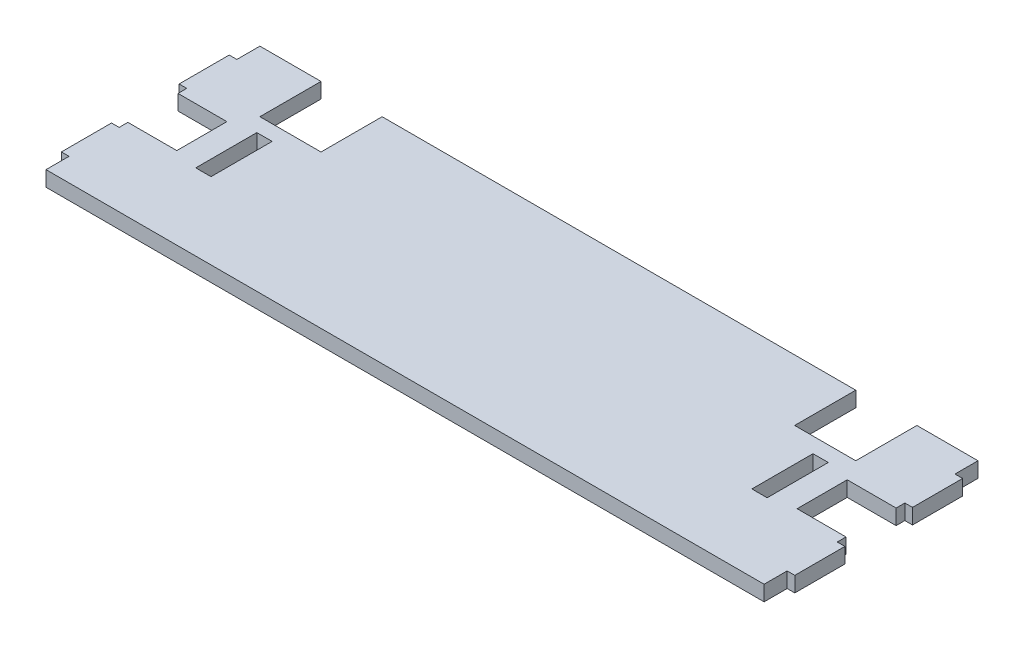
SolidWorks part; units mm, degrees
ref_plane "Front Plane" through (0, 0, 0) normal (0, 0, 1) x (1, 0, 0)
ref_plane "Top Plane" through (0, 0, 0) normal (0, 1, 0) x (1, 0, 0)
ref_plane "Right Plane" through (0, 0, 0) normal (1, 0, 0) x (0, 0, -1)
sketch "Sketch1" plane through (0, 0, 0) normal (0, 1, 0) x (1, 0, 0)
  line L0 (0, 72.39) -> (0, -44.45) construction
  line L1 (149.225, -44.45) -> (-149.225, -44.45)
  line L2 (149.225, -44.45) -> (149.225, -34.8747)
  line L3 (149.225, 44.45) -> (123.825, 44.45)
  line L4 (-149.225, -44.45) -> (-149.225, -34.8747)
  line L5 (149.225, -44.45) -> (-149.225, 44.45) construction
  line L6 (149.225, 44.45) -> (-149.225, -44.45) construction
  line L7 (149.225, 10.414) -> (128.905, 10.414)
  line L9 (149.225, -10.414) -> (128.905, -10.414)
  line L10 (128.905, 10.414) -> (128.905, -10.414)
  line L11 (-123.825, 44.45) -> (-149.225, 44.45)
  line L13 (-149.225, -10.414) -> (-128.905, -10.414)
  line L14 (-128.905, 10.414) -> (-128.905, -10.414)
  line L15 (-149.225, 10.414) -> (-128.905, 10.414)
  line L17 (-127, 0) -> (127, 0) construction
  line L18 (-149.225, 14.0467) -> (-152.4, 14.0467)
  line L20 (-149.225, 34.8747) -> (-152.4, 34.8747)
  line L21 (-152.4, 14.0467) -> (-152.4, 34.8747)
  line L22 (-149.225, -34.8747) -> (-152.4, -34.8747)
  line L23 (-152.4, -14.0467) -> (-152.4, -34.8747)
  line L24 (-149.225, -14.0467) -> (-152.4, -14.0467)
  line L27 (149.225, -14.0467) -> (152.4, -14.0467)
  line L28 (152.4, -14.0467) -> (152.4, -34.8747)
  line L29 (149.225, -34.8747) -> (152.4, -34.8747)
  line L30 (149.225, 34.8747) -> (152.4, 34.8747)
  line L31 (152.4, 14.0467) -> (152.4, 34.8747)
  line L32 (149.225, 14.0467) -> (152.4, 14.0467)
  line L34 (-149.225, 34.8747) -> (-149.225, 44.45)
  line L35 (-149.225, -14.0467) -> (-149.225, -10.414)
  line L36 (149.225, 34.8747) -> (149.225, 44.45)
  line L37 (149.225, -14.0467) -> (149.225, -10.414)
  line L38 (-149.225, 10.414) -> (-149.225, 14.0467)
  line L39 (149.225, 10.414) -> (149.225, 14.0467)
  line L40 (-123.825, 44.45) -> (-123.825, 19.05)
  line L41 (-123.825, 19.05) -> (-98.425, 19.05)
  line L42 (-98.425, 44.45) -> (-98.425, 19.05)
  line L44 (98.425, 44.45) -> (98.425, 19.05)
  line L45 (98.425, 19.05) -> (123.825, 19.05)
  line L46 (123.825, 44.45) -> (123.825, 19.05)
  line L47 (98.425, 44.45) -> (-98.425, 44.45)
  point P0 (0, 0)
  point P6 (127, 0)
  dimension "D1" = 298.45
  dimension "D2" = 88.9
  dimension "D3" = 20.828
  dimension "D5" = 3.175
  dimension "D6" = 20.828
  dimension "D4" = 20.32
  dimension "D7" = 25.4
  dimension "D8" = 25.4
  dimension "D9" = 25.4
  dimension "D10" = 25.4
  dimension "D12" = 25.4
  dimension "D11" = 25.4
  dimension "D13" = 304.8
extrude "Boss-Extrude1" add sketch "Sketch1" along normal mid plane 6.35
sketch "Sketch2" plane through (0, 0, 0) normal (0, 1, 0) x (1, 0, 0)
  line L1 (112.395, -12.7) -> (118.745, -12.7)
  line L2 (112.395, -12.7) -> (112.395, 12.7)
  line L3 (112.395, 12.7) -> (118.745, 12.7)
  line L4 (118.745, -12.7) -> (118.745, 12.7)
  line L5 (112.395, -12.7) -> (118.745, 12.7) construction
  line L6 (112.395, 12.7) -> (118.745, -12.7) construction
  line L7 (0, 44.45) -> (0, -44.45) construction
  line L8 (98.425, 44.45) -> (-98.425, 44.45) construction
  line L13 (128.905, -10.414) -> (128.905, 10.414) construction
  line L14 (-149.225, -44.45) -> (149.225, -44.45) construction
  line L15 (-112.395, -12.7) -> (-112.395, 12.7)
  line L16 (-112.395, -12.7) -> (-118.745, -12.7)
  line L17 (-118.745, -12.7) -> (-118.745, 12.7)
  line L18 (-112.395, 12.7) -> (-118.745, 12.7)
  point P0 (115.57, 0)
  point P10 (128.905, 0)
  dimension "D2" = 10.16
  dimension "D4" = 25.4
  dimension "D5" = 6.35
extrude "Cut-Extrude1" cut sketch "Sketch2" against normal through all both and the other way through all
equation "\"length\"= \"Avionics_Board_Length\""
equation "\"width\"=3.5"
equation "\"height\"= 0.25"
equation "\"D2@Sketch1\"=\"width\""
equation "\"eyebolt width\"= 0.82"
equation "\"eyebolt length\"= 0.8"
equation "\"D3@Sketch1\"=\"eyebolt width\""
equation "\"D4@Sketch1\"=\"eyebolt length\""
equation "\"lead screw holder height\"= 2.76"
equation "\"distance from holders to board\"=0.4"
equation "\"Mid_Coupler_Length\" = 12in"
equation "\"Avionics_Bulkhead_Thickness\" = 0.25in"
equation "\"Avionics_Bulkhead_Lip\" = 0.125in"
equation "\"Avionics_Board_Length\" = \"Mid_Coupler_Length\" - 2*\"Avionics_Bulkhead_Lip\""
equation "\"Body_Tube_OD\"= 4.024in"
equation "\"D1@Sketch1\"=\"length\""
